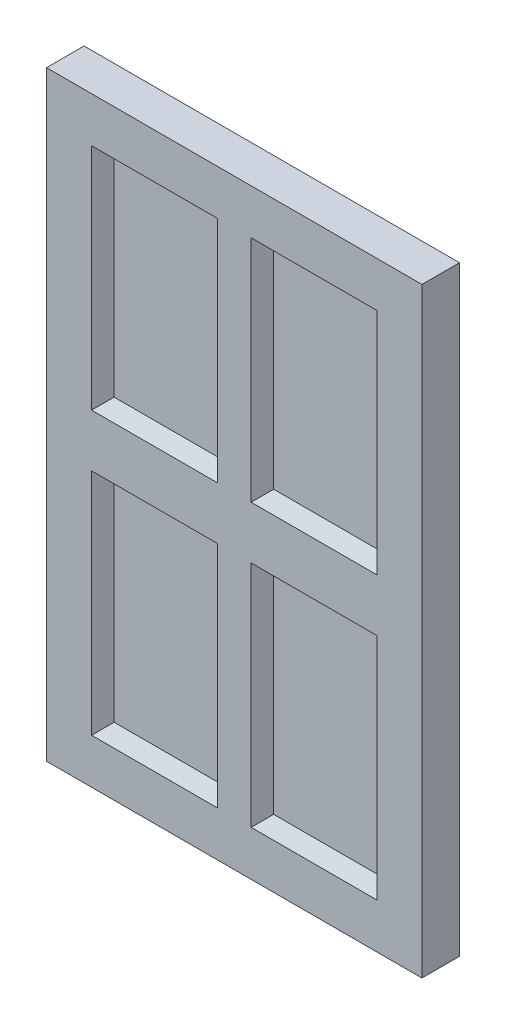
SolidWorks part; units mm, degrees
ref_plane "Front Plane" through (0, 0, 0) normal (0, 0, 1) x (1, 0, 0)
ref_plane "Top Plane" through (0, 0, 0) normal (0, 1, 0) x (1, 0, 0)
ref_plane "Right Plane" through (0, 0, 0) normal (1, 0, 0) x (0, 0, -1)
sketch "Sketch1" plane through (0, 0, 0) normal (0, 0, 1) x (1, 0, 0)
  line L1 (-50, 80) -> (50, 80)
  line L2 (-50, 80) -> (-50, -80)
  line L3 (-50, -80) -> (50, -80)
  line L4 (50, 80) -> (50, -80)
  line L5 (-50, 80) -> (50, -80) construction
  line L6 (-50, -80) -> (50, 80) construction
  point P0 (0, 0)
  dimension "D1" = 160
  dimension "D2" = 100
extrude "Boss-Extrude1" add sketch "Sketch1" along normal blind 10
sketch "Sketch2" plane through (0, 0, 10) normal (0, 0, 1) x (1, 0, 0)
  line L0 (2.5, 5) -> (40, 70) construction
  line L1 (-2.5, 5) -> (2.5, 5) construction
  line L2 (-2.5, 5) -> (-2.5, -5) construction
  line L3 (-2.5, -5) -> (2.5, -5) construction
  line L4 (2.5, 5) -> (2.5, -5) construction
  line L5 (-2.5, 5) -> (2.5, -5) construction
  line L6 (-2.5, -5) -> (2.5, 5) construction
  line L7 (-40, 70) -> (40, 70) construction
  line L8 (-40, 70) -> (-40, -70) construction
  line L9 (-40, -70) -> (40, -70) construction
  line L10 (40, 70) -> (40, -70) construction
  line L11 (-40, 70) -> (40, -70) construction
  line L12 (-40, -70) -> (40, 70) construction
  line L14 (2.5, 5) -> (40, 5)
  line L15 (2.5, 5) -> (2.5, 70)
  line L16 (2.5, 70) -> (40, 70)
  line L17 (40, 5) -> (40, 70)
  line L18 (2.5, 5) -> (40, 70) construction
  line L19 (2.5, 70) -> (40, 5) construction
  point P0 (0, 0)
  point P6 (0, 0)
  point P11 (21.25, 37.5)
  dimension "D1" = 5
  dimension "D2" = 10
  dimension "D3" = 80
  dimension "D4" = 140
extrude "Cut-Extrude1" cut sketch "Sketch2" against normal blind 3
mirror "Mirror5" about plane through (0, 0, 0) normal (0, 1, 0) of "Cut-Extrude1"
mirror "Mirror6" about plane through (0, 0, 0) normal (1, 0, 0) of "Mirror5"
ref_plane "Plane1" through (0, 0, 5) normal (0, 0, 1) x (1, 0, 0)
mirror "Mirror7" about plane through (0, 0, 5) normal (0, 0, 1) of "Mirror6", "Mirror5", "Cut-Extrude1"
chamfer "Chamfer2" distance 5 angle 45 32 edges at (-21.25, -5, 3) (-40, -37.5, 3) (-21.25, -70, 3) (-2.5, -37.5, 3) (-21.25, -70, 7) (-40, -37.5, 7) (-21.25, -5, 7) (-2.5, -37.5, 7) (21.25, 5, 3) (40, 37.5, 3) (21.25, 70, 3) (2.5, 37.5, 3) (-21.25, 70, 3) (-40, 37.5, 3) (-21.25, 5, 3) (-2.5, 37.5, 3) (21.25, -70, 3) (40, -37.5, 3) (21.25, -5, 3) (2.5, -37.5, 3) (21.25, -5, 7) (40, -37.5, 7) (21.25, -70, 7) (2.5, -37.5, 7) (21.25, 70, 7) (40, 37.5, 7) (21.25, 5, 7) (2.5, 37.5, 7) (-21.25, 5, 7) (-40, 37.5, 7) (-21.25, 70, 7) (-2.5, 37.5, 7)
